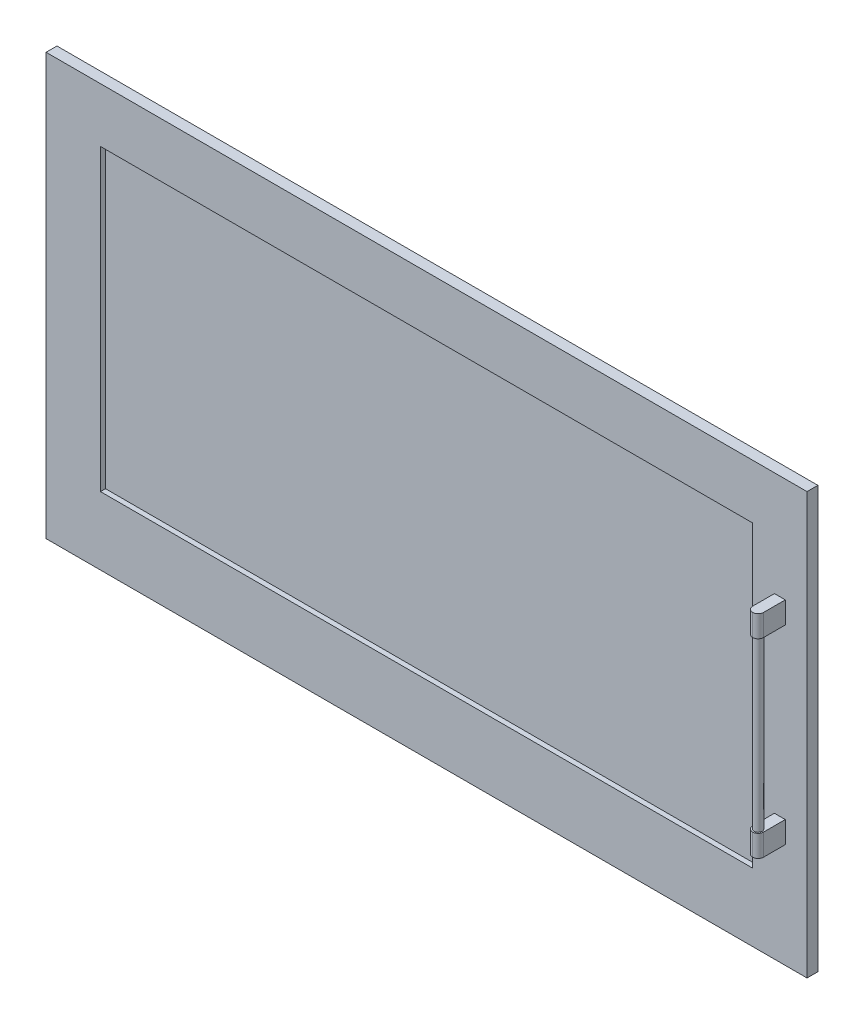
SolidWorks part; units mm, degrees
material "Water"
ref_plane "Front Plane" through (0, 0, 0) normal (0, 0, 1) x (1, 0, 0)
ref_plane "Top Plane" through (0, 0, 0) normal (0, 1, 0) x (1, 0, 0)
ref_plane "Right Plane" through (0, 0, 0) normal (1, 0, 0) x (0, 0, -1)
sketch "Sketch1" plane through (0, 0, 0) normal (0, 0, 1) x (1, 0, 0)
  line L1 (-1400, 775) -> (1400, 775)
  line L2 (-1400, 775) -> (-1400, -775)
  line L3 (-1400, -775) -> (1400, -775)
  line L4 (1400, 775) -> (1400, -775)
  line L5 (0, -775) -> (0, 775) construction
  line L6 (-1400, 0) -> (1400, 0) construction
  point P0 (0, 0)
extrude "Boss-Extrude1" add sketch "Sketch1" along normal blind 40
sketch "Sketch3" plane through (0, 0, 40) normal (0, 0, 1) x (1, 0, 0)
  line L0 (1400, -775) -> (1400, 775) construction
  line L1 (1280, 310) -> (1320, 310)
  line L2 (1280, 310) -> (1280, 390)
  line L3 (1280, 390) -> (1320, 390)
  line L4 (1320, 310) -> (1320, 390)
  line L5 (1300, 390) -> (1300, 310) construction
  line L6 (1280, 350) -> (1320, 350) construction
  point P0 (1300, 350)
  dimension "D1" = 350
  dimension "D2" = 100
  dimension "D3" = 40
extrude "Boss-Extrude4" add sketch "Sketch3" along normal blind 100
ref_plane "Plane1" through (0, 0, 20) normal (0, 0, 1) x (1, 0, 0)
fillet "Fillet1" radius 20 2 edges at (1280, 350, 140) (1320, 350, 140)
pattern_linear "LPattern1" count 2 spacing 700 along (0, -1, 0) of "Boss-Extrude4", "Fillet1"
sketch "Sketch4" plane through (0, -310, 0) normal (0, 1, 0) x (1, 0, 0)
  circle A0 centre (1300, -120) radius 15
extrude "Boss-Extrude5" add sketch "Sketch4" along normal up to surface (620 mm away) up to face at (1300, 310, 93.6569)
sketch "Sketch5" plane through (0, 0, 40) normal (0, 0, 1) x (1, 0, 0)
  line L0 (1400, 775) -> (-1400, 775) construction
  line L1 (-1200, 575) -> (1200, 575)
  line L2 (-1200, 575) -> (-1200, -525)
  line L3 (-1200, -525) -> (1200, -525)
  line L4 (1200, 575) -> (1200, -525)
  line L5 (-1400, -775) -> (1400, -775) construction
  line L6 (1400, -775) -> (1400, 775) construction
  line L7 (-1400, 775) -> (-1400, -775) construction
  dimension "D1" = 200
  dimension "D2" = 250
  dimension "D3" = 200
  dimension "D4" = 200
extrude "Cut-Extrude1" cut sketch "Sketch5" against normal blind 652
sketch "Sketch6" plane through (0, 0, 20) normal (0, 0, 1) x (1, 0, 0)
  line L0 (1200, 575) -> (-1200, 575) construction
  line L1 (-1199.5, 574.5) -> (1199.5, 574.5)
  line L2 (-1199.5, 574.5) -> (-1199.5, -524.5)
  line L3 (-1199.5, -524.5) -> (1199.5, -524.5)
  line L4 (1199.5, 574.5) -> (1199.5, -524.5)
  line L5 (-1200, 575) -> (-1200, -525) construction
  line L6 (1200, -525) -> (1200, 575) construction
  line L7 (-1200, -525) -> (1200, -525) construction
  dimension "D1" = 0.5
  dimension "D2" = 0.5
  dimension "D3" = 0.5
  dimension "D4" = 0.5
extrude "Boss-Extrude6" add sketch "Sketch6" along normal blind 2 and the other way blind 2 separate body
